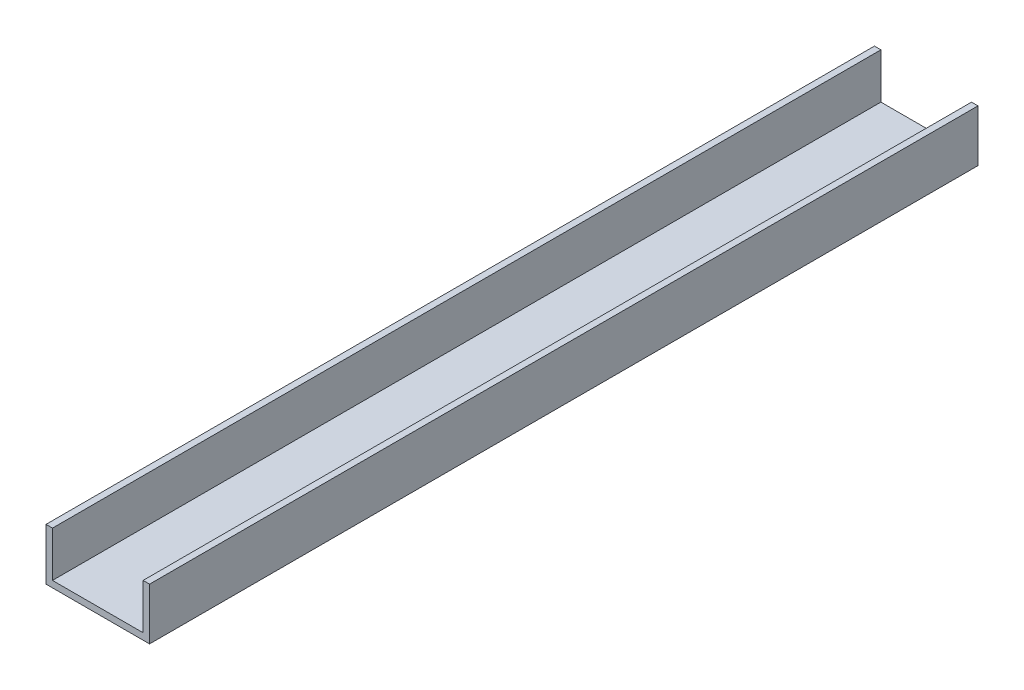
SolidWorks part; units mm, degrees
material "6063-T6"
ref_plane "Front" through (0, 0, 0) normal (0, 0, 1) x (1, 0, 0)
ref_plane "Top" through (0, 0, 0) normal (0, 1, 0) x (1, 0, 0)
ref_plane "Right" through (0, 0, 0) normal (1, 0, 0) x (0, 0, -1)
sketch "Sketch1" plane through (0, 0, 0) normal (0, 0, 1) x (1, 0, 0)
  line L0 (3.175, 3.175) -> (3.175, 25.4)
  line L1 (0, 0) -> (50.8, 0)
  line L2 (0, 0) -> (0, 25.4)
  line L4 (50.8, 0) -> (50.8, 25.4)
  line L5 (3.175, 3.175) -> (47.625, 3.175)
  line L6 (47.625, 3.175) -> (47.625, 25.4)
  line L7 (0, 25.4) -> (3.175, 25.4)
  line L8 (50.8, 25.4) -> (47.625, 25.4)
  dimension "D1" = 25.4
  dimension "D2" = 50.8
  dimension "D3" = 3.175
extrude "Boss-Extrude1" add sketch "Sketch1" along normal blind 406.4
